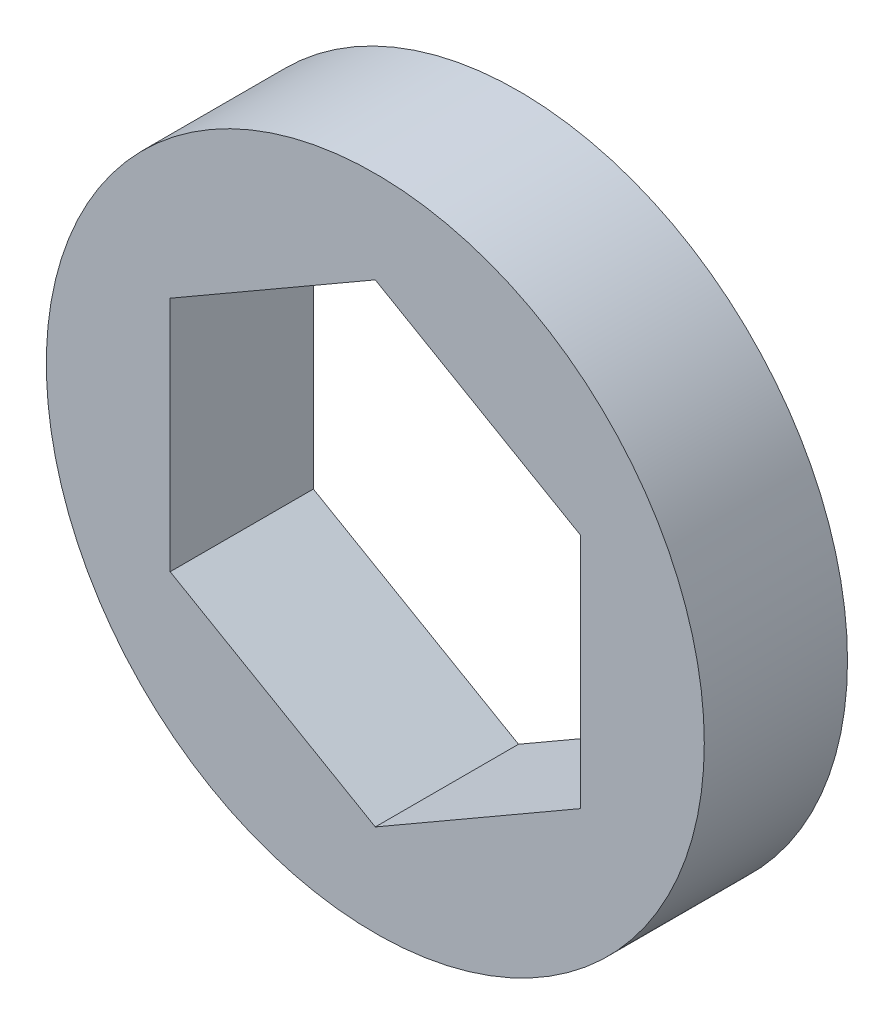
SolidWorks part; units mm, degrees
material "Nylon 101"
ref_plane "Front Plane" through (0, 0, 0) normal (0, 0, 1) x (1, 0, 0)
ref_plane "Top Plane" through (0, 0, 0) normal (0, 1, 0) x (1, 0, 0)
ref_plane "Right Plane" through (0, 0, 0) normal (1, 0, 0) x (0, 0, -1)
sketch "Sketch1" plane through (0, 0, 0) normal (0, 0, 1) x (1, 0, 0)
  line L1 (0, 7.7723) -> (-6.731, 3.8861)
  line L2 (-6.731, 3.8861) -> (-6.731, -3.8861)
  line L3 (-6.731, -3.8861) -> (0, -7.7723)
  line L4 (0, -7.7723) -> (6.731, -3.8861)
  line L5 (6.731, -3.8861) -> (6.731, 3.8861)
  line L6 (6.731, 3.8861) -> (0, 7.7723)
  circle A0 centre (0, 0) radius 6.731 construction
  circle A1 centre (0, 0) radius 10.795
  dimension "D1" = 13.462
  dimension "D2" = 21.59
extrude "Boss-Extrude1" add sketch "Sketch1" along normal blind 4.699
